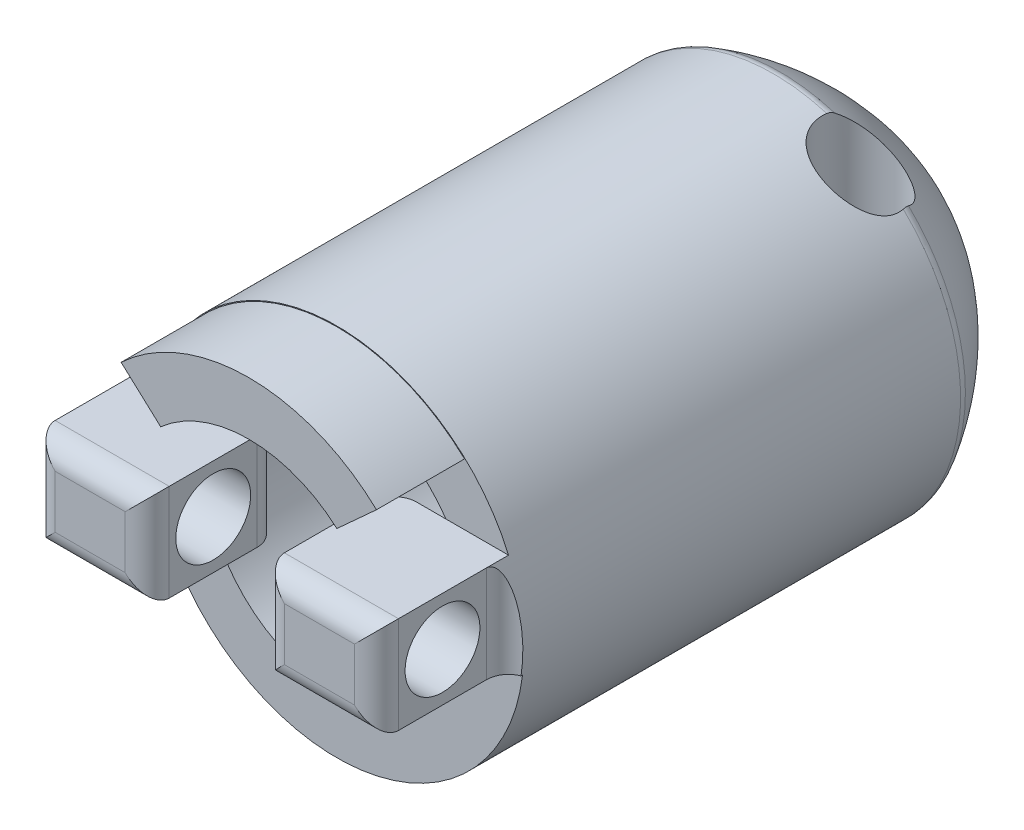
SolidWorks part; units mm, degrees
ref_plane "Front Plane" through (0, 0, 0) normal (0, 0, 1) x (1, 0, 0)
ref_plane "Top Plane" through (0, 0, 0) normal (0, 1, 0) x (1, 0, 0)
ref_plane "Right Plane" through (0, 0, 0) normal (1, 0, 0) x (0, 0, -1)
sketch "Sketch1" plane through (0, 0, 0) normal (0, 1, 0) x (1, 0, 0)
  line L0 (0, 0) -> (0, 26)
  line L1 (0, 0) -> (8.5, 0)
  line L2 (8.5, 0) -> (8.5, 20)
  line L3 (0, -55) -> (0, 55) construction
  arc A3 (0, 26) -> (8.5, 20) centre (-2.0464, 14.0801) cw
  dimension "D1" = 26
  dimension "D2" = 8.5
  dimension "D3" = 20
revolve "Revolve1" add sketch "Sketch1" angle 360 about L0
shell "Shell1" thickness 2.5 removed face at (8.5, 0, 0)
sketch "Sketch9" plane through (0, 0, 0) normal (0, 0, 1) x (1, 0, 0)
  line L0 (0, 3.9166) -> (0, -8.5) construction
  line L1 (-2.617, -1.0238) -> (-7.8007, -1.0238)
  line L2 (-2.617, -1.0238) -> (-2.617, 3.3762)
  line L3 (-2.617, 3.3762) -> (-7.8007, 3.3762)
  line L4 (-7.8007, -1.0238) -> (-7.8007, 3.3762)
  line L5 (-2.617, -1.0238) -> (-7.8007, 3.3762) construction
  line L6 (-2.617, 3.3762) -> (-7.8007, -1.0238) construction
  line L7 (2.617, -1.0238) -> (7.8007, -1.0238)
  line L8 (2.617, -1.0238) -> (2.617, 3.3762)
  line L9 (7.8007, -1.0238) -> (7.8007, 3.3762)
  line L10 (2.617, 3.3762) -> (7.8007, 3.3762)
  circle A0 centre (0, 0) radius 8.5 construction
  point P0 (-5.2089, 1.1762)
  dimension "D1" = 4.4
  dimension "D2" = 5.234
extrude "Boss-Extrude4" add sketch "Sketch9" along normal blind 6
sketch "Sketch12" plane through (7.8007, 0, 0) normal (1, 0, 0) x (0, 0, -1)
  line L0 (-6, 3.3762) -> (0, 3.3762) construction
  line L1 (-6, -1.0238) -> (-6, 3.3762) construction
  point P0 (-3, 1.1762)
  dimension "D1" = 2.2
  dimension "D2" = 3
fillet "Fillet1" radius 1 12 edges at (2.617, 1.1762, 0) (7.8007, 1.1762, 0) (-7.8007, 1.1762, 0) (-2.617, 1.1762, 0) (5.2089, 3.3762, 6) (7.8007, 1.1762, 6) (5.2089, -1.0238, 6) (2.617, 1.1762, 6) (-2.617, 1.1762, 6) (-5.2089, 3.3762, 6) (-7.8007, 1.1762, 6) (-5.2089, -1.0238, 6)
sketch "Sketch14" plane through (0, 0, 0) normal (0, 0, 1) x (1, 0, 0)
  line L1 (0, -9.35) -> (0, 9.35) construction
  line L3 (9.35, 0) -> (-9.35, 0) construction
  line L4 (-4.0039, 4.525) -> (-5.8016, 6.163)
  line L5 (4.0039, 4.525) -> (5.8016, 6.163)
  arc A3 (-5.8016, 6.163) -> (5.8016, 6.163) centre (0, 0) cw
  arc A5 (-4.0039, 4.525) -> (4.0039, 4.525) centre (0, 0) cw
extrude "Boss-Extrude5" add sketch "Sketch14" along normal blind 4
fillet "Fillet2" radius 0.6 1 edges at (8.5, 0, -20)
sketch "Sketch19" plane through (-7.8007, 0, 0) normal (-1, 0, 0) x (0, 0, 1)
  circle A0 centre (3, 1.1762) radius 1.7
  dimension "D1" = 3.4
extrude "Cut-Extrude5" cut sketch "Sketch19" against normal through all
sketch "Sketch21" plane through (0, 0, 0) normal (0, 1, 0) x (1, 0, 0)
  line L0 (0, -9.35) -> (0, 9.35) construction
  circle A0 centre (0, 18.862) radius 0.75
  dimension "D1" = 1.5
extrude "Cut-Extrude9" cut sketch "Sketch21" along normal blind 1 and the other way through all
sketch "Sketch22" plane through (0, 0, 0) normal (0, 1, 0) x (1, 0, 0)
  circle A0 centre (4.1605, 19.6338) radius 1.75
  dimension "D1" = 3.5
extrude "Cut-Extrude10" cut sketch "Sketch22" along normal through all
